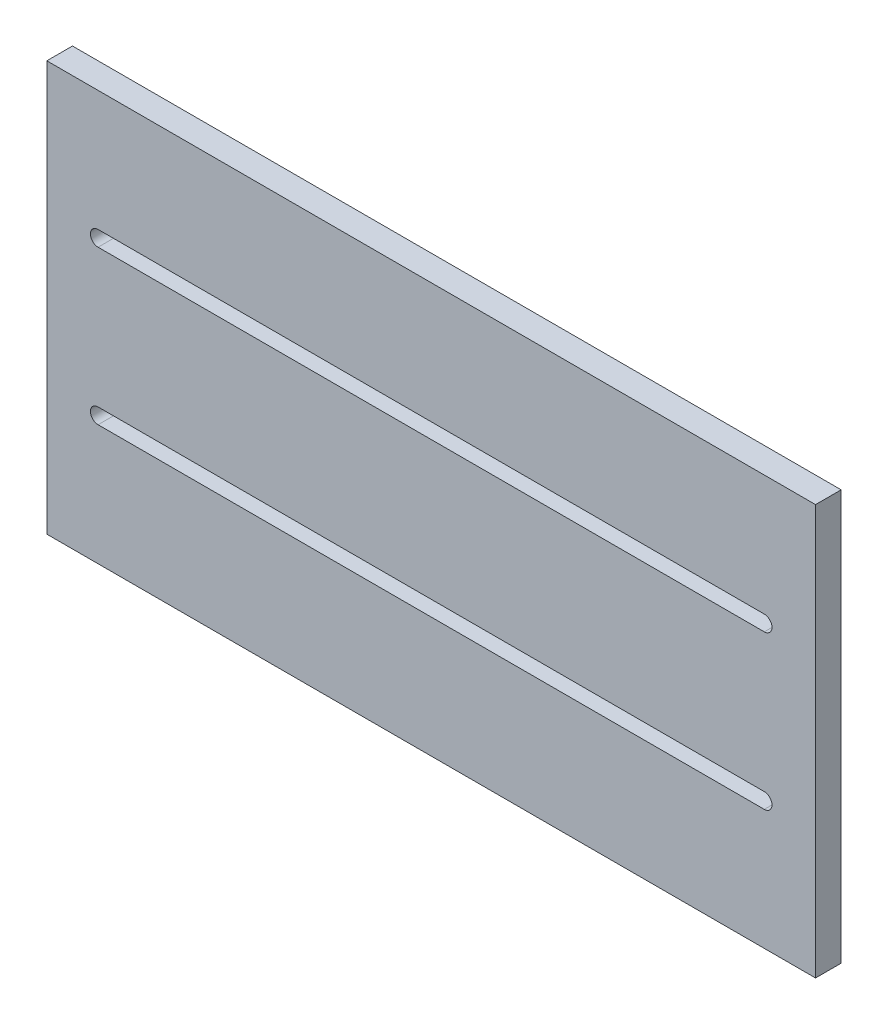
SolidWorks part; units mm, degrees
material "6061 Alloy"
ref_plane "Front Plane" through (0, 0, 0) normal (0, 0, 1) x (1, 0, 0)
ref_plane "Top Plane" through (0, 0, 0) normal (0, 1, 0) x (1, 0, 0)
ref_plane "Right Plane" through (0, 0, 0) normal (1, 0, 0) x (0, 0, -1)
sketch "Sketch1" plane through (0, 0, 0) normal (0, 1, 0) x (1, 0, 0)
  line L1 (0, 0) -> (190.5, 0)
  line L2 (0, 0) -> (0, 6.35)
  line L3 (0, 6.35) -> (190.5, 6.35)
  line L4 (190.5, 0) -> (190.5, 6.35)
  dimension "D1" = 190.5
  dimension "D2" = 6.35
extrude "Boss-Extrude1" add sketch "Sketch1" along normal blind 101.6
sketch "Sketch2" plane through (0, 0, -6.35) normal (0, 0, -1) x (-1, 0, 0)
  line L0 (-177.8, 71.755) -> (-12.7, 71.755)
  line L1 (-177.8, 67.945) -> (-12.7, 67.945)
  line L2 (-190.5, 0) -> (0, 0) construction
  line L3 (-179.705, 69.85) -> (-10.795, 69.85) construction
  line L4 (-190.5, 50.8) -> (0, 50.8) construction
  line L5 (-190.5, 101.6) -> (-190.5, 0) construction
  line L6 (0, 101.6) -> (0, 0) construction
  line L9 (-177.8, 33.655) -> (-12.7, 33.655)
  line L10 (-177.8, 29.845) -> (-12.7, 29.845)
  arc A0 (-12.7, 71.755) -> (-12.7, 67.945) centre (-12.7, 69.85) cw
  arc A1 (-177.8, 71.755) -> (-177.8, 67.945) centre (-177.8, 69.85) ccw
  arc A2 (-12.7, 29.845) -> (-12.7, 33.655) centre (-12.7, 31.75) ccw
  arc A3 (-177.8, 29.845) -> (-177.8, 33.655) centre (-177.8, 31.75) cw
  point P8 (-95.25, 0)
  point P9 (-95.25, 67.945)
  dimension "D1" = 3.81
  dimension "D2" = 165.1
  dimension "D3" = 69.85
extrude "Cut-Extrude1" cut sketch "Sketch2" against normal through all
